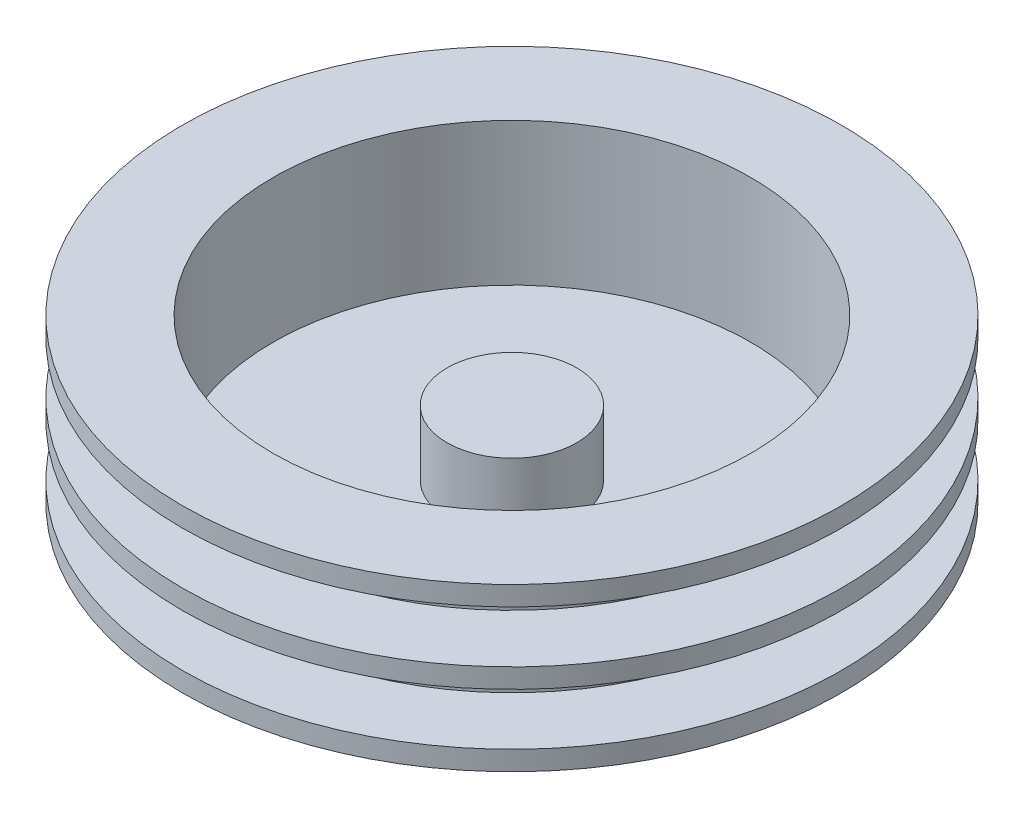
SolidWorks part; units mm, degrees
ref_plane "Front" through (0, 0, 0) normal (0, 0, 1) x (1, 0, 0)
ref_plane "Top" through (0, 0, 0) normal (0, 1, 0) x (1, 0, 0)
ref_plane "Right" through (0, 0, 0) normal (1, 0, 0) x (0, 0, -1)
sketch "Sketch1" plane through (0, 0, 0) normal (0, 1, 0) x (1, 0, 0)
  circle A0 centre (0, 0) radius 25.4
  circle A1 centre (0, 0) radius 20.066
  circle A2 centre (0, 0) radius 18.415
  circle A3 centre (0, 0) radius 5
  dimension "D1" = 50.8
  dimension "D2" = 40.132
  dimension "D3" = 36.83
  dimension "D4" = 10
extrude "Boss-Extrude1" add sketch "Sketch1" along normal blind 1.5 contours A0
extrude "Boss-Extrude2" add sketch "Sketch1<3>" along normal blind 4 from surface contours A1 A2 region at (-19.4984, 0, 0) starting at face at (0, 1.5, 25.4)
sketch "Sketch1<3>" plane through (0, 0, 0) normal (0, 1, 0) x (1, 0, 0) same geometry as "Sketch1"
extrude "Boss-Extrude3" add sketch "Sketch1<4>" along normal blind 1.5 from surface contours A0 A1 | A1 A2 region at (-24.6816, 0, 0) region at (-19.4984, 0, 0) starting at face at (0, 5.5, 20.066)
sketch "Sketch1<4>" plane through (0, 0, 0) normal (0, 1, 0) x (1, 0, 0) same geometry as "Sketch1"
extrude "Boss-Extrude4" add sketch "Sketch1<5>" along normal blind 4 from surface contours A1 A2 region at (-19.4984, 0, 0) starting at face at (0, 7, 25.4)
sketch "Sketch1<5>" plane through (0, 0, 0) normal (0, 1, 0) x (1, 0, 0) same geometry as "Sketch1"
extrude "Boss-Extrude5" add sketch "Sketch1<6>" along normal blind 1.5 from surface contours A0 A1 | A1 A2 region at (-24.6816, 0, 0) region at (-19.4984, 0, 0) starting at face at (0, 11, 20.066)
sketch "Sketch1<6>" plane through (0, 0, 0) normal (0, 1, 0) x (1, 0, 0) same geometry as "Sketch1"
extrude "Boss-Extrude6" add sketch "Sketch1<7>" along normal blind 5 from surface contours A3 region at (0, 0, 0) starting at face at (0, 1.5, 20.066)
sketch "Sketch1<7>" plane through (0, 0, 0) normal (0, 1, 0) x (1, 0, 0) same geometry as "Sketch1"
